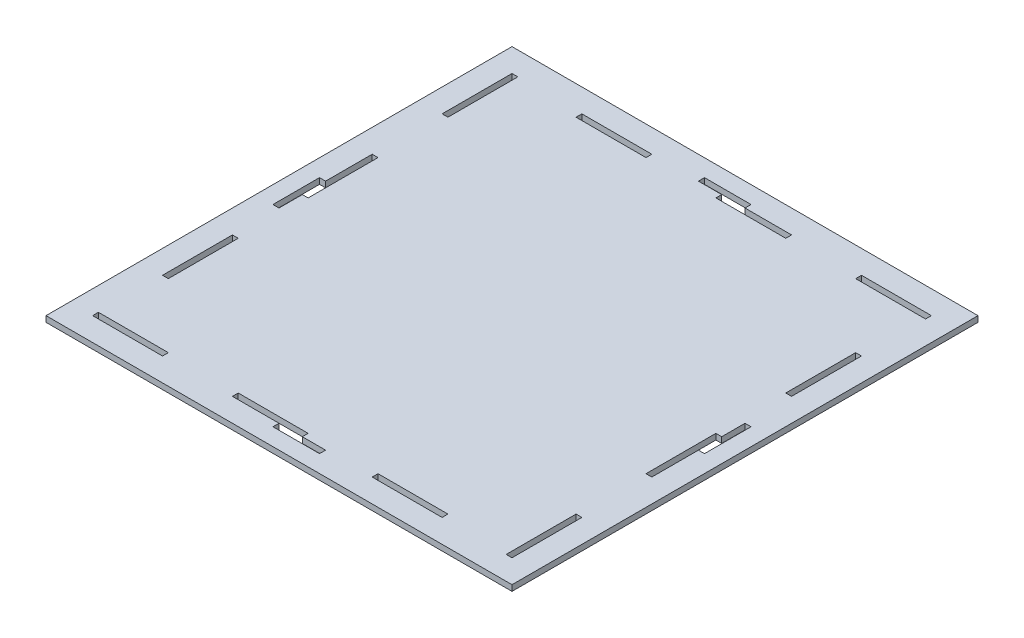
SolidWorks part; units mm, degrees
material "Acrylic (Medium-high impact)"
ref_plane "Front Plane" through (0, 0, 0) normal (0, 0, 1) x (1, 0, 0)
ref_plane "Top Plane" through (0, 0, 0) normal (0, 1, 0) x (1, 0, 0)
ref_plane "Right Plane" through (0, 0, 0) normal (1, 0, 0) x (0, 0, -1)
sketch "Sketch1" plane through (0, 0, 0) normal (0, 1, 0) x (1, 0, 0)
  line L0 (-76.2, 114.3) -> (-76.2, 111.125)
  line L1 (-114.3, 114.3) -> (114.3, 114.3)
  line L2 (-114.3, 114.3) -> (-114.3, -114.3)
  line L3 (-114.3, -114.3) -> (114.3, -114.3)
  line L4 (114.3, 114.3) -> (114.3, -114.3)
  line L5 (-114.3, 114.3) -> (-76.2, 114.3)
  line L6 (-114.3, 114.3) -> (-114.3, 111.125)
  line L7 (-114.3, 111.125) -> (-76.2, 111.125)
  line L8 (-76.2, 114.3) -> (-76.2, 111.125)
  line L9 (-76.2, 114.3) -> (-38.1, 114.3)
  line L10 (-38.1, 114.3) -> (-38.1, 111.125)
  line L11 (-76.2, 111.125) -> (-38.1, 111.125)
  line L12 (-38.1, 114.3) -> (-38.1, 111.125)
  line L13 (-38.1, 114.3) -> (0, 114.3)
  line L14 (0, 114.3) -> (0, 111.125)
  line L15 (-38.1, 111.125) -> (0, 111.125)
  line L16 (0, 114.3) -> (0, 111.125)
  line L17 (0, 114.3) -> (38.1, 114.3)
  line L18 (38.1, 114.3) -> (38.1, 111.125)
  line L19 (0, 111.125) -> (38.1, 111.125)
  line L20 (38.1, 114.3) -> (38.1, 111.125)
  line L21 (38.1, 114.3) -> (76.2, 114.3)
  line L22 (76.2, 114.3) -> (76.2, 111.125)
  line L23 (38.1, 111.125) -> (76.2, 111.125)
  line L24 (76.2, 114.3) -> (76.2, 111.125)
  line L25 (76.2, 114.3) -> (114.3, 114.3)
  line L26 (114.3, 114.3) -> (114.3, 111.125)
  line L27 (76.2, 111.125) -> (114.3, 111.125)
  line L76 (-76.2, -114.3) -> (-76.2, -111.125)
  line L77 (-114.3, -114.3) -> (-76.2, -114.3)
  line L78 (-114.3, -114.3) -> (-114.3, -111.125)
  line L79 (-114.3, -111.125) -> (-76.2, -111.125)
  line L80 (-76.2, -114.3) -> (-76.2, -111.125)
  line L81 (-76.2, -114.3) -> (-38.1, -114.3)
  line L82 (-38.1, -114.3) -> (-38.1, -111.125)
  line L83 (-76.2, -111.125) -> (-38.1, -111.125)
  line L84 (-38.1, -114.3) -> (-38.1, -111.125)
  line L85 (-38.1, -114.3) -> (0, -114.3)
  line L86 (0, -114.3) -> (0, -111.125)
  line L87 (-38.1, -111.125) -> (0, -111.125)
  line L88 (0, -114.3) -> (0, -111.125)
  line L89 (0, -114.3) -> (38.1, -114.3)
  line L90 (38.1, -114.3) -> (38.1, -111.125)
  line L91 (0, -111.125) -> (38.1, -111.125)
  line L92 (38.1, -114.3) -> (38.1, -111.125)
  line L93 (38.1, -114.3) -> (76.2, -114.3)
  line L94 (76.2, -114.3) -> (76.2, -111.125)
  line L95 (38.1, -111.125) -> (76.2, -111.125)
  line L96 (76.2, -114.3) -> (76.2, -111.125)
  line L97 (76.2, -114.3) -> (114.3, -114.3)
  line L98 (114.3, -114.3) -> (114.3, -111.125)
  line L99 (76.2, -111.125) -> (114.3, -111.125)
  line L148 (-114.3, 76.2) -> (-114.3, 38.1)
  line L149 (-114.3, 114.3) -> (-111.125, 114.3)
  line L150 (-114.3, 114.3) -> (-114.3, 76.2)
  line L151 (-114.3, 76.2) -> (-111.125, 76.2)
  line L152 (-111.125, 114.3) -> (-111.125, 76.2)
  line L153 (-114.3, 76.2) -> (-111.125, 76.2)
  line L154 (-111.125, 76.2) -> (-111.125, 38.1)
  line L155 (-114.3, 38.1) -> (-111.125, 38.1)
  line L156 (-114.3, 38.1) -> (-114.3, 0)
  line L157 (-114.3, 38.1) -> (-111.125, 38.1)
  line L158 (-111.125, 38.1) -> (-111.125, 0)
  line L159 (-114.3, 0) -> (-111.125, 0)
  line L160 (-114.3, 0) -> (-114.3, -38.1)
  line L161 (-114.3, 0) -> (-111.125, 0)
  line L162 (-111.125, 0) -> (-111.125, -38.1)
  line L163 (-114.3, -38.1) -> (-111.125, -38.1)
  line L164 (-114.3, -38.1) -> (-114.3, -76.2)
  line L165 (-114.3, -38.1) -> (-111.125, -38.1)
  line L166 (-111.125, -38.1) -> (-111.125, -76.2)
  line L167 (-114.3, -76.2) -> (-111.125, -76.2)
  line L168 (-114.3, -76.2) -> (-114.3, -114.3)
  line L169 (-114.3, -76.2) -> (-111.125, -76.2)
  line L170 (-111.125, -76.2) -> (-111.125, -114.3)
  line L171 (-114.3, -114.3) -> (-111.125, -114.3)
  line L220 (111.125, 76.2) -> (111.125, 38.1)
  line L221 (111.125, 114.3) -> (114.3, 114.3)
  line L222 (111.125, 114.3) -> (111.125, 76.2)
  line L223 (111.125, 76.2) -> (114.3, 76.2)
  line L224 (114.3, 114.3) -> (114.3, 76.2)
  line L225 (111.125, 76.2) -> (114.3, 76.2)
  line L226 (114.3, 76.2) -> (114.3, 38.1)
  line L227 (111.125, 38.1) -> (114.3, 38.1)
  line L228 (111.125, 38.1) -> (111.125, 0)
  line L229 (111.125, 38.1) -> (114.3, 38.1)
  line L230 (114.3, 38.1) -> (114.3, 0)
  line L231 (111.125, 0) -> (114.3, 0)
  line L232 (111.125, 0) -> (111.125, -38.1)
  line L233 (111.125, 0) -> (114.3, 0)
  line L234 (114.3, 0) -> (114.3, -38.1)
  line L235 (111.125, -38.1) -> (114.3, -38.1)
  line L236 (111.125, -38.1) -> (111.125, -76.2)
  line L237 (111.125, -38.1) -> (114.3, -38.1)
  line L238 (114.3, -38.1) -> (114.3, -76.2)
  line L239 (111.125, -76.2) -> (114.3, -76.2)
  line L240 (111.125, -76.2) -> (111.125, -114.3)
  line L241 (111.125, -76.2) -> (114.3, -76.2)
  line L242 (114.3, -76.2) -> (114.3, -114.3)
  line L243 (111.125, -114.3) -> (114.3, -114.3)
  line L292 (0, 114.3) -> (0, -114.3) construction
  line L293 (-127, 127) -> (127, 127)
  line L294 (-127, 127) -> (-127, -127)
  line L295 (-127, -127) -> (127, -127)
  line L296 (127, 127) -> (127, -127)
  line L297 (-127, 127) -> (127, -127) construction
  line L298 (-127, -127) -> (127, 127) construction
  line L299 (-12.7, 117.602) -> (12.7, 117.602)
  line L300 (-12.7, 117.602) -> (-12.7, 114.3)
  line L301 (-12.7, 114.3) -> (12.7, 114.3)
  line L302 (12.7, 117.602) -> (12.7, 114.3)
  line L303 (114.3, 12.7) -> (117.602, 12.7)
  line L304 (114.3, 12.7) -> (114.3, -12.7)
  line L305 (114.3, -12.7) -> (117.602, -12.7)
  line L306 (117.602, 12.7) -> (117.602, -12.7)
  line L307 (-12.7, -117.602) -> (12.7, -117.602)
  line L308 (-12.7, -117.602) -> (-12.7, -114.3)
  line L309 (-12.7, -114.3) -> (12.7, -114.3)
  line L310 (12.7, -117.602) -> (12.7, -114.3)
  line L311 (-114.3, -12.7) -> (-117.602, -12.7)
  line L312 (-114.3, -12.7) -> (-114.3, 12.7)
  line L313 (-114.3, 12.7) -> (-117.602, 12.7)
  line L314 (-117.602, -12.7) -> (-117.602, 12.7)
  line L315 (114.3, 0) -> (-114.3, 0) construction
  point P5 (0, 114.3)
  point P7 (-114.3, 0)
  point P32 (0, 0)
  dimension "D1" = 228.6
  dimension "D2" = 228.6
  dimension "D3" = 38.1
  dimension "D4" = 3.175
  dimension "D7" = 38.1
  dimension "D8" = 3.175
  dimension "D11" = 12.7
  dimension "D12" = 3.302
  dimension "D13" = 25.4
  dimension "D5" = 6
  dimension "D6" = 6
  dimension "D9" = 6
  dimension "D10" = 6
extrude "Boss-Extrude1" add sketch "Sketch1" along normal blind 3.175 contours L5 L152 L7 L0 | L10 L15 L14 L1 | L18 L23 L22 L1 | L222 L223 L4 L27 | L228 L231 L4 L227 | L236 L239 L4 L235 | L240 L99 L94 L3 | L91 L86 L3 L90 | L83 L76 L3 L82 | L170 L167 L2 L79 | L2 L163 L162 L159 | L2 L155 L154 L151 | L240 L236 L232 L228 L220 L222 L27 L23 L19 L15 L11 L7 L152 L154 L158 L162 L166 L170 L79 L83 L87 L91 L95 L99 | L296 L293 L294 L295 L311 L314 L313 L2 L1 L5 L300 L299 L302 L17 L25 L4 L303 L306 L305 L234 L97 L3 L89 L310 L307 L308 L77 L160 region at (-93.6625, 0, -112.7125) region at (0, 0, 0) region at (-19.05, 0, -112.7125) region at (-112.7125, 0, -57.15) region at (57.15, 0, -112.7125) region at (-112.7125, 0, 19.05) region at (112.7125, 0, -93.6625) region at (-112.7125, 0, 93.6625) region at (112.7125, 0, -19.05) region at (-57.15, 0, 112.7125) region at (112.7125, 0, 57.15) region at (19.05, 0, 112.7125) region at (93.6625, 0, 112.7125) region at (0, 0, -123.4079)
equation "\"D7@Sketch1\"=\"D1@Sketch1\"/\"D5@Sketch1\""
equation "\"D3@Sketch1\"=\"D2@Sketch1\"/\"D9@Sketch1\""
